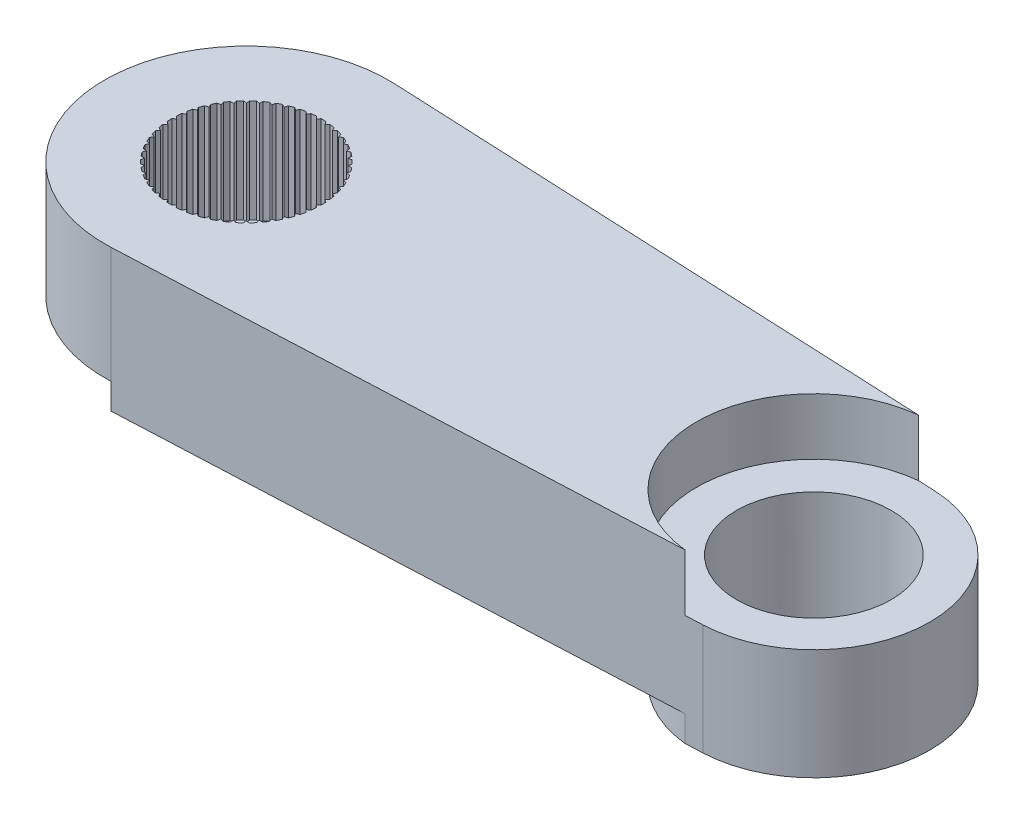
SolidWorks part; units mm, degrees
ref_plane "Front Plane" through (0, 0, 0) normal (0, 0, 1) x (1, 0, 0)
ref_plane "Top Plane" through (0, 0, 0) normal (0, 1, 0) x (1, 0, 0)
ref_plane "Right Plane" through (0, 0, 0) normal (1, 0, 0) x (0, 0, -1)
sketch "Sketch1" plane through (0, 0, 0) normal (0, 1, 0) x (1, 0, 0)
  line L0 (0.25, 5.4943) -> (22.2045, 4.4953)
  line L1 (22.2045, -4.4953) -> (0.25, -5.4943)
  circle A0 centre (0, 0) radius 1.5
  circle A1 centre (22, 0) radius 3
  arc A2 (0.25, 5.4943) -> (0.25, -5.4943) centre (0, 0) ccw
  arc A3 (22.2045, 4.4953) -> (22.2045, -4.4953) centre (22, 0) cw
  dimension "D2" = 6
  dimension "D3" = 3
  dimension "D4" = 4.5
  dimension "D5" = 5.5
  dimension "D1" = 22
extrude "Boss-Extrude1" add sketch "Sketch1" along normal blind 3.5 contours A0 | A1 | L1 A2 L0 A3 region at (0, 0, 0) region at (22, 0, 0)
sketch "Sketch2" plane through (0, 3.5, 0) normal (0, 1, 0) x (1, 0, 0)
  circle A0 centre (0, 0) radius 2.9
  circle A3 centre (0, 0) radius 4.7
  dimension "D1" = 5.8
  dimension "D2" = 9.4
extrude "Boss-Extrude2" add sketch "Sketch2" along normal blind 3
sketch "Sketch3" plane through (0, 3.5, 0) normal (0, 1, 0) x (1, 0, 0)
  circle A0 centre (0, 0) radius 2.9 construction
  circle A1 centre (0, 0) radius 2.9
extrude "Cut-Extrude1" cut sketch "Sketch3" against normal blind 1
sketch "Sketch4" plane through (0, 3.5, 0) normal (0, 1, 0) x (1, 0, 0)
  line L2 (22.2045, 4.4953) -> (0.25, 5.4943)
  line L3 (0.25, -5.4943) -> (22.2045, -4.4953)
  line L4 (22.2045, 4.4953) -> (0.25, 5.4943)
  line L5 (0.25, -5.4943) -> (22.2045, -4.4953)
  circle A1 centre (0, 0) radius 1.5 construction
  arc A2 (22.2045, -4.4953) -> (22.2045, 4.4953) centre (22, 0) ccw
  arc A3 (0.25, 5.4943) -> (0.25, -5.4943) centre (0, 0) ccw
  arc A4 (22.2045, -4.4953) -> (22.2045, 4.4953) centre (22, 0) ccw
  arc A5 (0.25, 5.4943) -> (0.25, -5.4943) centre (0, 0) ccw
  circle A6 centre (0, 0) radius 1.5
  circle A7 centre (22, 0) radius 3 construction
  circle A8 centre (22, 0) radius 3
  circle A9 centre (0, 0) radius 2.9 construction
  circle A10 centre (0, 0) radius 2.9
  circle M8 centre (0, 0) radius 4.7
  arc M9 (22.2045, -4.4953) -> (22.2045, 4.4953) centre (22, 0) ccw
  line M10 (22.2045, 4.4953) -> (0.25, 5.4943)
  arc M11 (0.25, 5.4943) -> (0.25, -5.4943) centre (0, 0) ccw
  line M12 (0.25, -5.4943) -> (22.2045, -4.4953)
  circle M13 centre (22, 0) radius 3
  dimension "D1" = 0
extrude "Boss-Extrude3" add sketch "Sketch4" along normal blind 1.8 contours M12 M9 M10 M11 M13 M8 region at (11.7364, 3.5, 0)
sketch "Sketch5" plane through (0, 0, 0) normal (0, -1, 0) x (1, 0, 0)
  line L2 (22.2045, 4.4953) -> (0.25, 5.4943)
  line L3 (0.25, -5.4943) -> (22.2045, -4.4953)
  line L4 (22.2045, 4.4953) -> (0.25, 5.4943)
  line L5 (0.25, -5.4943) -> (22.2045, -4.4953)
  arc A2 (22.2045, -4.4953) -> (22.2045, 4.4953) centre (22, 0) ccw
  arc A3 (0.25, 5.4943) -> (0.25, -5.4943) centre (0, 0) ccw
  arc A4 (22.2045, -4.4953) -> (22.2045, 4.4953) centre (22, 0) ccw
  arc A5 (0.25, 5.4943) -> (0.25, -5.4943) centre (0, 0) ccw
  dimension "D1" = 0
extrude "Cut-Extrude2" cut sketch "Sketch5" against normal blind 1
sketch "Sketch6" plane through (0, 5.3, 0) normal (0, 1, 0) x (1, 0, 0)
  line L0 (0.25, -5.4943) -> (22.2045, -4.4953) construction
  line L2 (22.2045, 4.4953) -> (0.25, 5.4943) construction
  line L5 (0.25, -5.4943) -> (22.2045, -4.4953)
  line L6 (22.2045, 4.4953) -> (0.25, 5.4943)
  line L7 (0.25, -5.4943) -> (22.8765, -4.4648)
  line L8 (22.8765, 4.4648) -> (0.25, 5.4943)
  arc A0 (22.8765, -4.4648) -> (22.8765, 4.4648) centre (22, 0) cw
  arc A2 (22.2045, -4.4953) -> (22.2045, 4.4953) centre (22, 0) ccw construction
  arc A3 (22.2045, -4.4953) -> (22.2045, 4.4953) centre (22, 0) ccw
  arc A4 (0.25, 5.4943) -> (0.25, -5.4943) centre (0, 0) ccw
  arc A6 (0.25, 5.4943) -> (0.25, -5.4943) centre (0, 0) ccw
  circle A7 centre (22, 0) radius 3 construction
  line M5 (0.25, -5.4943) -> (22.2045, -4.4953)
  arc M8 (0.25, 5.4943) -> (0.25, -5.4943) centre (0, 0) ccw
  circle M10 centre (0, 0) radius 4.7
  dimension "D1" = 4.55
  dimension "D2" = 0
extrude "Boss-Extrude4" add sketch "Sketch6" along normal blind 1 contours A0 L8 M5 M8 M10 region at (9.5191, 5.3, 0)
sketch "Sketch7" plane through (0, 5.3, 0) normal (0, 1, 0) x (1, 0, 0)
  line L2 (22.2045, 4.4953) -> (21.5326, 4.5259)
  line L3 (21.5326, -4.5259) -> (22.2045, -4.4953)
  line L4 (22.2045, 4.4953) -> (21.5326, 4.5259)
  line L5 (21.5326, -4.5259) -> (22.2045, -4.4953)
  circle A0 centre (22, 0) radius 3 construction
  circle A1 centre (22, 0) radius 3
  arc A2 (21.5326, 4.5259) -> (21.5326, -4.5259) centre (22, 0) ccw
  arc A3 (22.2045, -4.4953) -> (22.2045, 4.4953) centre (22, 0) ccw
  arc A4 (21.5326, 4.5259) -> (21.5326, -4.5259) centre (22, 0) ccw
  arc A5 (22.2045, -4.4953) -> (22.2045, 4.4953) centre (22, 0) ccw
  dimension "D1" = 0
extrude "Cut-Extrude3" cut sketch "Sketch7" against normal blind 1
extrude "Boss-Extrude5" add sketch "Sketch7<2>" against normal blind 1 from surface starting at face at (0, 1, -1.5)
sketch "Sketch7<2>" plane through (0, 5.3, 0) normal (0, 1, 0) x (1, 0, 0) same geometry as "Sketch7"
sketch "Sketch8" plane through (0, 2.5, 0) normal (0, 1, 0) x (1, 0, 0)
  line L0 (2.8944, -0.1808) -> (2.7944, -0.0913)
  line L1 (2.7944, -0.0913) -> (2.9, -0.0085)
  arc A0 (2.9, -0.0085) -> (2.8944, -0.1808) centre (0, 0) cw
  circle A1 centre (0, 0) radius 2.9 construction
  dimension "D1" = 0.1
extrude "Boss-Extrude6" add sketch "Sketch8" along normal up to surface (4 mm away) contours L1 A0 L0 up to face at (0, 6.5, 4.7)
pattern_circular "CirPattern1" count 50 over 360 about axis through (0, 6.5, 0) along (0, 1, 0) of "Boss-Extrude6" reverse direction yes
sketch "Sketch9" plane through (0, 1, 0) normal (0, -1, 0) x (1, 0, 0)
  circle A0 centre (0, 0) radius 5.5
  dimension "D1" = 11
extrude "Cut-Extrude4" cut sketch "Sketch9" against normal blind 1
sketch "Sketch10" plane through (0, 6.3, 0) normal (0, 1, 0) x (1, 0, 0)
  line L2 (0.25, -5.4943) -> (21.5326, -4.5259)
  line L3 (21.5326, 4.5259) -> (0.25, 5.4943)
  line L4 (0.25, -5.4943) -> (21.5326, -4.5259)
  line L5 (21.5326, 4.5259) -> (0.25, 5.4943)
  circle A0 centre (0, 0) radius 4.7 construction
  circle A1 centre (0, 0) radius 4.7
  arc A2 (21.5326, 4.5259) -> (21.5326, -4.5259) centre (22, 0) ccw
  arc A3 (0.25, 5.4943) -> (0.25, -5.4943) centre (0, 0) ccw
  arc A4 (21.5326, 4.5259) -> (21.5326, -4.5259) centre (22, 0) ccw
  arc A5 (0.25, 5.4943) -> (0.25, -5.4943) centre (0, 0) ccw
  circle M5 centre (0, 0) radius 4.7
  dimension "D1" = 0
extrude "Boss-Extrude7" add sketch "Sketch10" along normal up to surface (0.2 mm away) contours M5 | L4 A4 L5 A5 region at (0, 6.3, 0) up to face at (0, 6.5, 4.7)
